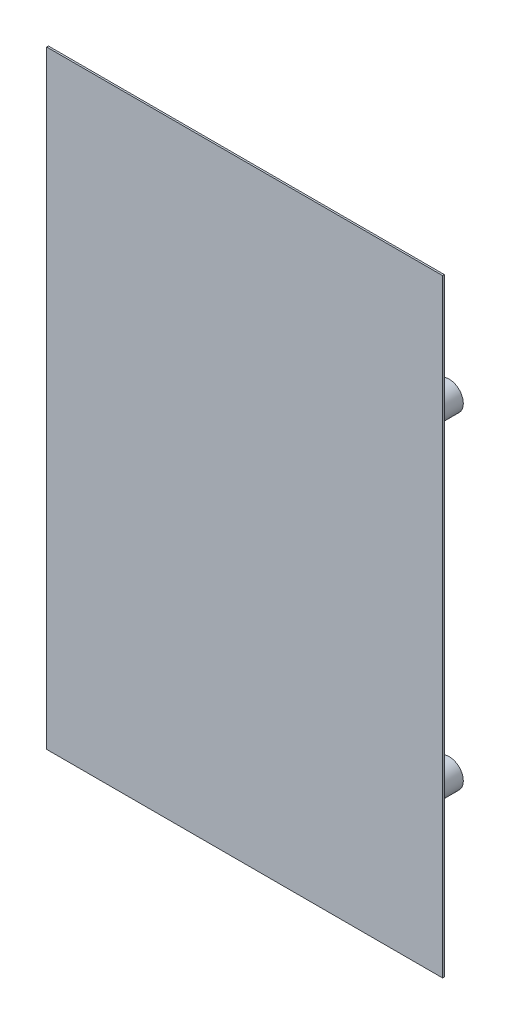
SolidWorks part; units mm, degrees
ref_plane "Front Plane" through (0, 0, 0) normal (0, 0, 1) x (1, 0, 0)
ref_plane "Top Plane" through (0, 0, 0) normal (0, 1, 0) x (1, 0, 0)
ref_plane "Right Plane" through (0, 0, 0) normal (1, 0, 0) x (0, 0, -1)
sketch "Sketch1" plane through (0, 0, 0) normal (0, 0, 1) x (1, 0, 0)
  line L1 (109, 159.3091) -> (-4, 159.3091)
  line L2 (109, 159.3091) -> (109, -14.3091)
  line L3 (109, -14.3091) -> (-4, -14.3091)
  line L4 (-4, 159.3091) -> (-4, -14.3091)
extrude "Boss-Extrude1" add sketch "Sketch1" along normal blind 0.5
sketch "Sketch2" plane through (0, 0, 0) normal (0, 0, -1) x (-1, 0, 0)
  circle A0 centre (-5.6, 25.85) radius 2 construction
  circle A1 centre (-99.4, 25.85) radius 2 construction
  circle A2 centre (-99.4, 119.15) radius 2 construction
  circle A3 centre (-5.6, 119.15) radius 2 construction
  circle A4 centre (-5.6, 25.85) radius 2
  circle A5 centre (-99.4, 25.85) radius 2
  circle A6 centre (-99.4, 119.15) radius 2
  circle A7 centre (-5.6, 119.15) radius 2
  circle A8 centre (-5.6, 119.15) radius 4
  circle A9 centre (-5.6, 25.85) radius 4
  circle A10 centre (-99.4, 25.85) radius 4
  circle A11 centre (-99.4, 119.15) radius 4
  dimension "D1" = 8
extrude "Boss-Extrude2" add sketch "Sketch2" along normal up to surface (11 mm away)
sketch "Sketch3" plane through (0, 0, 0) normal (0, 0, -1) x (-1, 0, 0)
  line L0 (-99.4, 119.15) -> (-5.6, 119.15) construction
  line L1 (-7.3321, 122.15) -> (-8.2458, 122.15)
  line L2 (-9.0641, 119.15) -> (-7.3321, 116.15)
  line L3 (-7.3321, 116.15) -> (-3.8679, 116.15)
  line L4 (-3.8679, 116.15) -> (-2.1359, 119.15)
  line L5 (-2.1359, 119.15) -> (-3.8679, 122.15)
  line L6 (-3.8679, 122.15) -> (-7.3321, 122.15)
  line L7 (-7.3321, 122.15) -> (-9.0641, 119.15)
  line L8 (-7.3321, 116.15) -> (-8.2458, 116.15)
  line L9 (-52.5, 159.3091) -> (-52.5, -14.3091) construction
  line L10 (-109, 159.3091) -> (4, 159.3091) construction
  line L11 (4, -14.3091) -> (-109, -14.3091) construction
  line L12 (-97.6679, 116.15) -> (-96.7542, 116.15)
  line L13 (-97.6679, 122.15) -> (-95.9359, 119.15)
  line L14 (-95.9359, 119.15) -> (-97.6679, 116.15)
  line L15 (-97.6679, 116.15) -> (-101.1321, 116.15)
  line L16 (-101.1321, 116.15) -> (-102.8641, 119.15)
  line L17 (-102.8641, 119.15) -> (-101.1321, 122.15)
  line L18 (-101.1321, 122.15) -> (-97.6679, 122.15)
  line L19 (-97.6679, 122.15) -> (-96.7542, 122.15)
  line L20 (-109, 72.5) -> (4, 72.5) construction
  line L21 (-109, -14.3091) -> (-109, 159.3091) construction
  line L22 (4, 159.3091) -> (4, -14.3091) construction
  line L23 (-7.3321, 28.85) -> (-8.2458, 28.85)
  line L24 (-7.3321, 28.85) -> (-3.8679, 28.85)
  line L25 (-9.0641, 25.85) -> (-7.3321, 28.85)
  line L26 (-2.1359, 25.85) -> (-3.8679, 22.85)
  line L27 (-3.8679, 28.85) -> (-2.1359, 25.85)
  line L28 (-7.3321, 22.85) -> (-9.0641, 25.85)
  line L29 (-3.8679, 22.85) -> (-7.3321, 22.85)
  line L30 (-7.3321, 22.85) -> (-8.2458, 22.85)
  line L31 (-97.6679, 22.85) -> (-96.7542, 22.85)
  line L32 (-101.1321, 22.85) -> (-97.6679, 22.85)
  line L33 (-102.8641, 25.85) -> (-101.1321, 22.85)
  line L34 (-101.1321, 28.85) -> (-102.8641, 25.85)
  line L35 (-97.6679, 28.85) -> (-101.1321, 28.85)
  line L36 (-95.9359, 25.85) -> (-97.6679, 28.85)
  line L37 (-97.6679, 22.85) -> (-95.9359, 25.85)
  line L38 (-97.6679, 28.85) -> (-96.7542, 28.85)
  circle A0 centre (-5.6, 119.15) radius 3 construction
  circle A1 centre (-5.6, 119.15) radius 4 construction
  circle A2 centre (-5.6, 119.15) radius 4 construction
  circle M15 centre (-99.4, 119.15) radius 4
  circle M16 centre (-99.4, 25.85) radius 4
  circle M17 centre (-5.6, 25.85) radius 4
  circle M18 centre (-5.6, 119.15) radius 4
  dimension "D1" = 6
extrude "Cut-Extrude1" cut sketch "Sketch3" along normal blind 3 contours L18 L17 L16 L15 L14 L13 | L19 L13 L14 L12 M15 | L6 L7 L2 L3 L4 L5 | L8 L2 L7 L1 M18 | L29 L26 L27 L24 L25 L28 | L30 L28 L25 L23 M17 | L32 L37 L36 L35 L34 L33 | L38 L36 L37 L31 M16 region at (8.2536, 120.6821, 0) region at (5.6, 119.15, 0) region at (96.7464, 117.6179, 0) region at (99.4, 119.15, 0) region at (8.2536, 27.3821, 0) region at (5.6, 25.85, 0) region at (96.7464, 24.3179, 0) region at (99.4, 25.85, 0)
